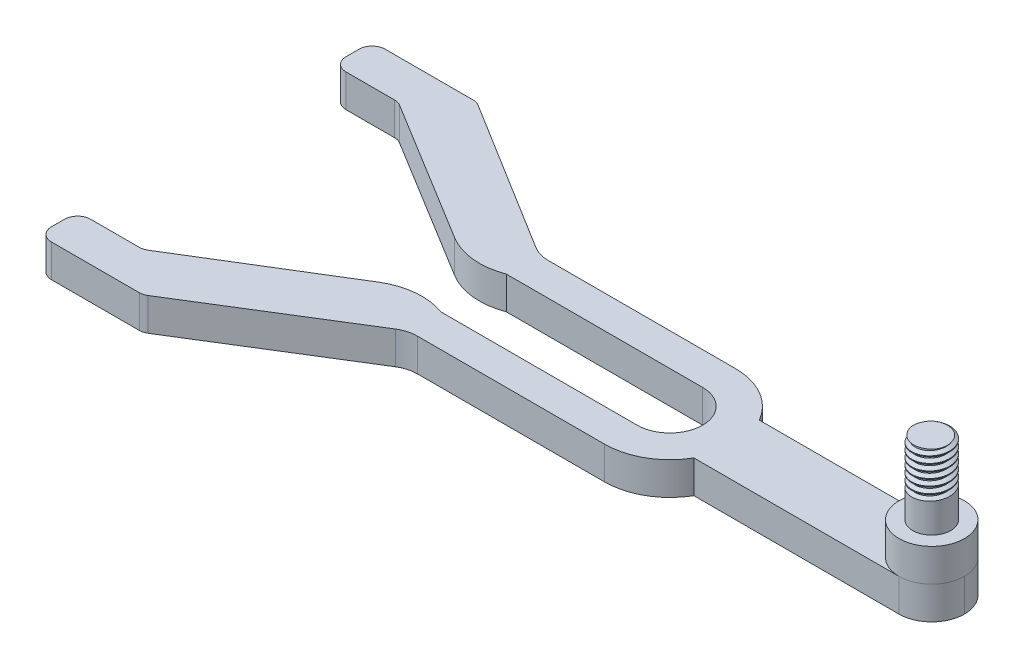
SolidWorks part; units mm, degrees
ref_plane "前视基准面" through (0, 0, 0) normal (0, 0, 1) x (1, 0, 0)
ref_plane "上视基准面" through (0, 0, 0) normal (0, 1, 0) x (1, 0, 0)
ref_plane "右视基准面" through (0, 0, 0) normal (1, 0, 0) x (0, 0, -1)
sketch "草图1" plane through (0, 0, 0) normal (0, 1, 0) x (1, 0, 0)
  line L1 (25, -5) -> (-25, -5)
  line L2 (25, -5) -> (25, 5)
  line L3 (25, 5) -> (-25, 5)
  line L4 (-25, -5) -> (-25, 5)
  line L5 (25, -5) -> (-25, 5) construction
  line L6 (25, 5) -> (-25, -5) construction
  point P0 (0, 0)
  dimension "D1" = 10
  dimension "D2" = 50
extrude "凸台-拉伸1" add sketch "草图1" along normal blind 5
sketch "草图2" plane through (0, 5, 0) normal (0, 1, 0) x (1, 0, 0)
  line L0 (25, -5) -> (25, 5) construction
  circle A0 centre (20, 0) radius 2.9
  dimension "D1" = 5.8
  dimension "D2" = 5
extrude "凸台-拉伸2" add sketch "草图2" along normal blind 16
sketch "草图3" plane through (0, 5, 0) normal (0, 1, 0) x (1, 0, 0)
  circle A0 centre (20, 0) radius 5
  dimension "D1" = 10
extrude "凸台-拉伸3" add sketch "草图3" along normal blind 5
fillet "圆角1" radius 5 2 edges at (25, 2.5, 5) (25, 2.5, -5)
thread "螺纹线1" pitch 1 method cut profile "螺纹线轮廓1" start angle 0, offset 1, length 7, pitch 1, diameter 5.8
ref_plane "基准面1" through (17.1, 22, 0) normal (0, 0, 1) x (-1, 0, 0)
sketch "螺纹线轮廓1" plane through (17.1, 22, 0) normal (0, 0, 1) x (-1, 0, 0)
  line L0 (0, 0) -> (0, 1) construction
  line L11 (0, 0) -> (0, 0.875)
  line L12 (0, 0.875) -> (-0.5413, 0.5625)
  line L13 (-0.5413, 0.5625) -> (-0.5413, 0.3125)
  line L15 (-0.5413, 0.3125) -> (0, 0)
  line L17 (-0.5413, 0.4375) -> (0, 0.4375) construction
  point P2 (0, 0)
  dimension "Pitch" = 1
  dimension "Profile_Angle" = 60
  dimension "Profile_Land" = 0.25
  dimension "Profile_Height" = 0.5413
sketch "草图11" plane through (0, 5, 0) normal (0, 1, 0) x (1, 0, 0)
  line L0 (-30, 0) -> (-20, 0) construction
  line L1 (-30, 10) -> (-20, 10)
  line L2 (-30, -10) -> (-20, -10)
  line L3 (-25, 5) -> (-25, -5) construction
  arc A0 (-30, 10) -> (-30, -10) centre (-30, 0) ccw
  arc A1 (-20, -10) -> (-20, 10) centre (-20, 0) ccw
  point P3 (-25, 0)
  dimension "D1" = 10
  dimension "D2" = 10
extrude "凸台-拉伸4" add sketch "草图11" against normal blind 5
sketch "草图13" plane through (0, 5, 0) normal (0, 1, 0) x (1, 0, 0)
  line L0 (-20, 0) -> (-30, 0) construction
  line L1 (-20, -5) -> (-30, -5)
  line L2 (-20, 5) -> (-30, 5)
  line L3 (-20, 10) -> (-30, 10) construction
  arc A0 (-20, -5) -> (-20, 5) centre (-20, 0) ccw
  arc A1 (-30, 5) -> (-30, -5) centre (-30, 0) ccw
  point P4 (-25, 0)
  dimension "D1" = 5
extrude "切除-拉伸2" cut sketch "草图13" against normal blind 5
sketch "草图14" plane through (0, 5, 0) normal (0, 1, 0) x (1, 0, 0)
  line L1 (-30, 5) -> (-50, 5)
  line L2 (-30, 5) -> (-30, -5)
  line L3 (-30, -5) -> (-50, -5)
  line L4 (-50, 5) -> (-50, -5)
  dimension "D1" = 20
extrude "切除-拉伸3" cut sketch "草图14" against normal blind 5
sketch "草图15" plane through (0, 5, 0) normal (0, 1, 0) x (1, 0, 0)
  line L0 (-20, 5) -> (-38.6603, 5) construction
  line L1 (-30, 10) -> (-50, 10)
  line L2 (-30, 10) -> (-30, 5)
  line L3 (-30, 5) -> (-50, 5)
  line L4 (-50, 10) -> (-50, 5)
  line L5 (-15, 0) -> (-160.6515, 0) construction
  line L6 (-50, -10) -> (-50, -5)
  line L7 (-30, -5) -> (-50, -5)
  line L8 (-30, -10) -> (-30, -5)
  line L9 (-30, -10) -> (-50, -10)
  arc A0 (-20, -5) -> (-20, 5) centre (-20, 0) ccw construction
  dimension "D1" = 20
extrude "凸台-拉伸5" add sketch "草图15" against normal blind 5
sketch "草图16" plane through (0, 5, 0) normal (0, 1, 0) x (1, 0, 0)
  line L0 (-50, 10) -> (-75, 25.5)
  line L1 (-75, 25.5) -> (-81, 25.5)
  line L2 (-81, 25.5) -> (-81, 19.5)
  line L5 (-50, 5) -> (-50, 10)
  line L8 (-50, 5) -> (-50, 0.5)
  line L9 (-50, 0.5) -> (-81, 19.5)
  dimension "D1" = 15.5
  dimension "D2" = 25
  dimension "D3" = 6
  dimension "D4" = 4.5
  dimension "D5" = 6
extrude "凸台-拉伸6" add sketch "草图16" against normal blind 5
mirror "镜向1" about plane through (0, 0, 0) normal (0, 0, 1) of "凸台-拉伸6"
fillet "圆角4" radius 5 2 edges at (-50, 2.5, -10) (-50, 2.5, 10)
sketch "草图19" plane through (0, 5, 0) normal (0, 1, 0) x (1, 0, 0)
  line L0 (-81, 19.5) -> (-50, 0.5) construction
  line L1 (-81, 25.5) -> (-91, 25.5)
  line L2 (-81, 25.5) -> (-81, 19.5)
  line L3 (-81, 19.5) -> (-91, 19.5)
  line L4 (-91, 25.5) -> (-91, 19.5)
  line L5 (0, 0) -> (-91, 0) construction
  line L6 (-91, -25.5) -> (-91, -19.5)
  line L7 (-81, -19.5) -> (-91, -19.5)
  line L8 (-81, -25.5) -> (-81, -19.5)
  line L9 (-81, -25.5) -> (-91, -25.5)
  dimension "D1" = 10
extrude "凸台-拉伸7" add sketch "草图19" against normal up to surface (5 mm away) up to face at (-39.2585, 0, 0)
fillet "圆角5" radius 10 2 edges at (-50, 2.5, 0.5) (-50, 2.5, -0.5)
fillet "圆角6" radius 2 8 edges at (-81, 2.5, 19.5) (-81, 2.5, -19.5) (-75, 2.5, -25.5) (-75, 2.5, 25.5) (-91, 2.5, 25.5) (-91, 2.5, 19.5) (-91, 2.5, -19.5) (-91, 2.5, -25.5)
